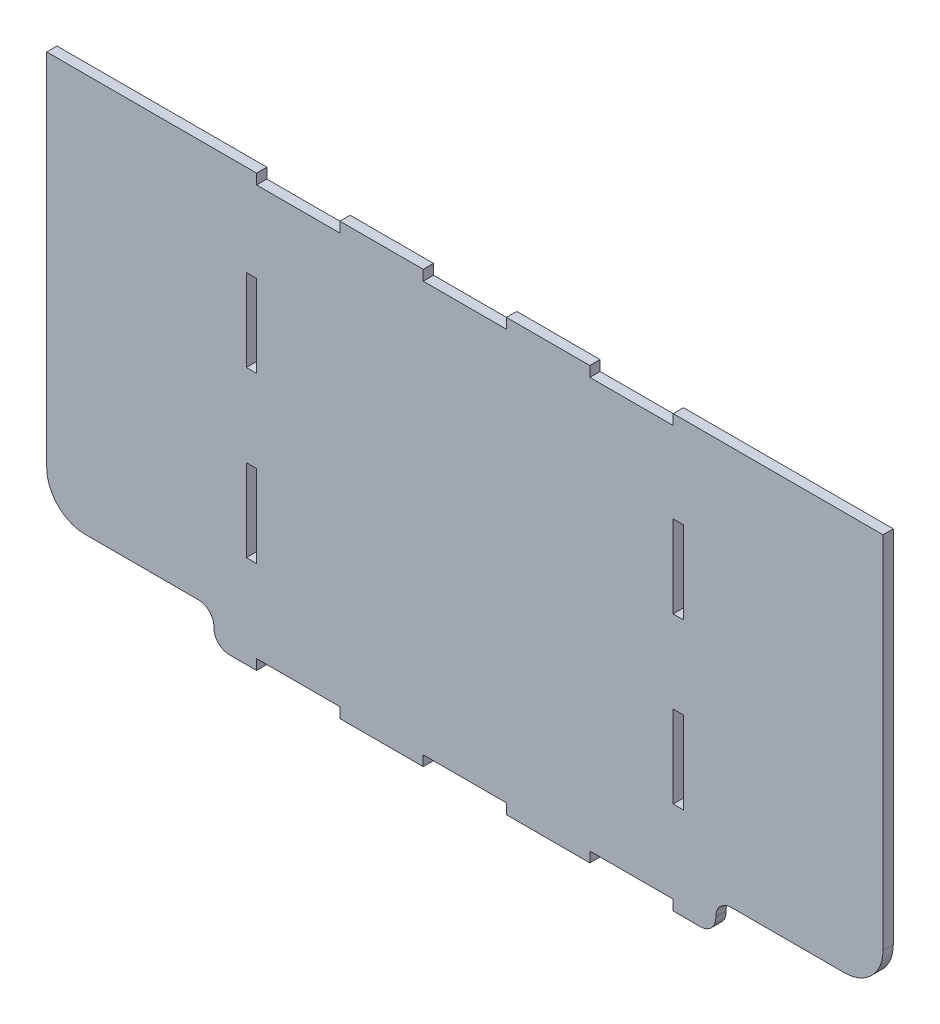
SolidWorks part; units mm, degrees
material "A-Glass Fiber"
ref_plane "Front Plane" through (0, 0, 0) normal (0, 0, 1) x (1, 0, 0)
ref_plane "Top Plane" through (0, 0, 0) normal (0, 1, 0) x (1, 0, 0)
ref_plane "Right Plane" through (0, 0, 0) normal (1, 0, 0) x (0, 0, -1)
sketch "Sketch1" plane through (0, 0, 0) normal (0, 0, 1) x (1, 0, 0)
  line L0 (0, 0) -> (1345.4471, 0)
  line L1 (212.2829, -469.9) -> (1133.1642, -469.9)
  line L2 (0, 0) -> (188.5098, -454.2888)
  line L3 (1345.4471, 0) -> (1156.9372, -454.2888)
  spline S1 degree 3 poles (1156.9372, -454.2888) (1155.9652, -456.6313) (1154.631, -458.8169) (1152.2259, -461.6935) (1151.3551, -462.5908) (1149.4733, -464.2609) (1148.4599, -465.0331) (1146.3603, -466.4012) (1145.2664, -467.0047) (1142.9909, -468.0521) (1141.799, -468.4985) (1138.1745, -469.5606) (1135.6993, -469.9116) (1133.1642, -469.9) knots 0 0 0 0 0.25 0.25 0.375 0.375 0.5 0.5 0.625 0.625 0.75 0.75 1 1 1 1
  spline S2 degree 3 poles (188.5098, -454.2888) (189.4819, -456.6313) (190.8161, -458.8169) (193.2211, -461.6935) (194.092, -462.5908) (195.9737, -464.2609) (196.9872, -465.0331) (199.0868, -466.4012) (200.1807, -467.0047) (202.4562, -468.0521) (203.6481, -468.4985) (207.2726, -469.5606) (209.7478, -469.9116) (212.2829, -469.9) knots 0 0 0 0 0.25 0.25 0.375 0.375 0.5 0.5 0.625 0.625 0.75 0.75 1 1 1 1
  dimension "D1" = 112.536
  dimension "D2" = 112.536
  dimension "D3" = 920.8813
  dimension "D4" = 469.9
extrude "Boss-Extrude1" add sketch "Sketch1" along normal blind 10.16
ref_plane "Plane1" through (672.7235, 0, 0) normal (1, 0, 0) x (0, 0, -1)
sketch "Sketch2" plane through (0, 0, 10.16) normal (0, 0, 1) x (1, 0, 0)
  line L0 (467.0082, -378.4231) -> (467.0082, -297.1061) construction
  line L1 (467.0082, -297.1061) -> (456.8417, -297.1061) construction
  line L2 (456.8417, -297.1061) -> (456.8417, -378.4231) construction
  line L3 (456.8417, -378.4231) -> (467.0082, -378.4231) construction
  line L4 (878.4388, -297.1061) -> (878.4388, -378.4231) construction
  line L5 (878.4388, -378.4231) -> (888.6053, -378.4231) construction
  line L6 (888.6053, -378.4231) -> (888.6053, -297.1061) construction
  line L7 (888.6053, -297.1061) -> (878.4388, -297.1061) construction
  line L8 (878.4388, -134.4722) -> (878.4388, -215.7892) construction
  line L9 (878.4388, -215.7892) -> (888.6053, -215.7892) construction
  line L10 (888.6053, -215.7892) -> (888.6053, -134.4722) construction
  line L11 (888.6053, -134.4722) -> (878.4388, -134.4722) construction
  line L24 (467.0082, -215.7892) -> (467.0082, -134.4722) construction
  line L25 (467.0082, -134.4722) -> (456.8417, -134.4722) construction
  line L26 (456.8417, -134.4722) -> (456.8417, -215.7892) construction
  line L27 (456.8417, -215.7892) -> (467.0082, -215.7892) construction
  line L28 (878.4388, -469.9) -> (878.4388, -459.74) construction
  line L29 (878.4388, -459.74) -> (796.1675, -459.74) construction
  line L30 (796.1675, -469.9) -> (796.1675, -459.74) construction
  line L31 (713.8592, -469.9) -> (713.8592, -459.74) construction
  line L32 (631.5879, -459.74) -> (713.8592, -459.74) construction
  line L33 (631.5879, -469.9) -> (631.5879, -459.74) construction
  line L34 (467.0082, -469.9) -> (467.0082, -459.74) construction
  line L35 (549.2795, -469.9) -> (549.2795, -459.74) construction
  line L36 (467.0082, -459.74) -> (549.2795, -459.74) construction
  line L37 (467.0082, -378.4231) -> (467.0082, -297.1061)
  line L38 (467.0082, -297.1061) -> (456.8417, -297.1061)
  line L39 (456.8417, -297.1061) -> (456.8417, -378.4231)
  line L40 (456.8417, -378.4231) -> (467.0082, -378.4231)
  line L41 (878.4388, -297.1061) -> (878.4388, -378.4231)
  line L42 (878.4388, -378.4231) -> (888.6053, -378.4231)
  line L43 (888.6053, -378.4231) -> (888.6053, -297.1061)
  line L44 (888.6053, -297.1061) -> (878.4388, -297.1061)
  line L45 (878.4388, -134.4722) -> (878.4388, -215.7892)
  line L46 (878.4388, -215.7892) -> (888.6053, -215.7892)
  line L47 (888.6053, -215.7892) -> (888.6053, -134.4722)
  line L48 (888.6053, -134.4722) -> (878.4388, -134.4722)
  line L61 (467.0082, -215.7892) -> (467.0082, -134.4722)
  line L62 (467.0082, -134.4722) -> (456.8417, -134.4722)
  line L63 (456.8417, -134.4722) -> (456.8417, -215.7892)
  line L64 (456.8417, -215.7892) -> (467.0082, -215.7892)
  line L65 (878.4388, -469.9) -> (878.4388, -459.74)
  line L66 (878.4388, -459.74) -> (796.1675, -459.74)
  line L67 (796.1675, -469.9) -> (796.1675, -459.74)
  line L68 (713.8592, -469.9) -> (713.8592, -459.74)
  line L69 (631.5879, -459.74) -> (713.8592, -459.74)
  line L70 (631.5879, -469.9) -> (631.5879, -459.74)
  line L71 (467.0082, -469.9) -> (467.0082, -459.74)
  line L72 (549.2795, -469.9) -> (549.2795, -459.74)
  line L73 (467.0082, -459.74) -> (549.2795, -459.74)
  line L74 (467.0082, -469.9) -> (549.2795, -469.9)
  line L75 (631.5879, -469.9) -> (713.8592, -469.9)
  line L76 (796.1675, -469.9) -> (878.4388, -469.9)
extrude "Cut-Extrude2" cut sketch "Sketch2" against normal blind 137.414
sketch "Sketch4" plane through (0, 0, 10.16) normal (0, 0, 1) x (1, 0, 0)
  line L0 (0, 0) -> (1345.4471, 0)
  line L1 (1345.4471, 0) -> (1327.0023, -44.45)
  line L2 (1156.9372, -454.2888) -> (1345.4471, 0) construction
  line L3 (1327.0023, -44.45) -> (18.4448, -44.45)
  line L4 (0, 0) -> (188.5098, -454.2888) construction
  line L5 (18.4448, -44.45) -> (0, 0)
  dimension "D1" = 44.45
extrude "Cut-Extrude3" cut sketch "Sketch4" against normal through all
sketch "Sketch5" plane through (0, 0, 10.16) normal (0, 0, 1) x (1, 0, 0)
  line L0 (672.7235, -5.588) -> (672.7235, 5.588) construction
  line L1 (713.8715, -54.61) -> (631.5755, -54.61)
  line L2 (713.8715, -54.61) -> (713.8715, -44.45)
  line L3 (713.8715, -44.45) -> (631.5755, -44.45)
  line L4 (631.5755, -54.61) -> (631.5755, -44.45)
  line L5 (713.8715, -54.61) -> (631.5755, -44.45) construction
  line L6 (713.8715, -44.45) -> (631.5755, -54.61) construction
  line L7 (18.4448, -44.45) -> (1327.0023, -44.45) construction
  line L9 (631.5755, -44.45) -> (549.2795, -44.45)
  line L10 (631.5755, -44.45) -> (631.5755, -54.61)
  line L11 (631.5755, -54.61) -> (549.2795, -54.61)
  line L12 (549.2795, -44.45) -> (549.2795, -54.61)
  line L13 (549.2795, -44.45) -> (466.9835, -44.45)
  line L14 (549.2795, -44.45) -> (549.2795, -54.61)
  line L15 (549.2795, -54.61) -> (466.9835, -54.61)
  line L16 (466.9835, -44.45) -> (466.9835, -54.61)
  line L17 (713.8715, -44.45) -> (796.1675, -44.45)
  line L18 (713.8715, -44.45) -> (713.8715, -54.61)
  line L19 (713.8715, -54.61) -> (796.1675, -54.61)
  line L20 (796.1675, -44.45) -> (796.1675, -54.61)
  line L21 (796.1675, -44.45) -> (878.4635, -44.45)
  line L22 (796.1675, -44.45) -> (796.1675, -54.61)
  line L23 (796.1675, -54.61) -> (878.4635, -54.61)
  line L24 (878.4635, -44.45) -> (878.4635, -54.61)
  point P0 (672.7235, -49.53)
  line M26 (1327.0023, -44.45) -> (18.4448, -44.45)
  dimension "D1" = 82.296
  dimension "D2" = 10.16
extrude "Cut-Extrude4" cut sketch "Sketch5" against normal through all contours L16 L15 L12 M26 | L4 L1 L2 M26 | L24 L20 L23 M26 region at (672.7235, -49.53, 10.16) region at (837.3155, -49.53, 10.16) region at (508.1315, -49.53, 10.16)
sketch "Sketch6" plane through (0, 0, 10.16) normal (0, 0, 1) x (1, 0, 0)
  line L0 (192.8075, -448.0779) -> (224.9829, -469.9)
  line L2 (212.2829, -469.9) -> (467.0082, -469.9) construction
  line L4 (56.5448, -44.45) -> (56.5448, -119.699)
  line L5 (24.3099, -42.0162) -> (194.3749, -451.8551)
  line L6 (56.5448, -119.699) -> (192.8075, -448.0779)
  line L7 (18.4448, -44.45) -> (466.9835, -44.45) construction
  line L9 (56.5448, -44.45) -> (-120.2389, 37.3825)
  line L10 (-120.2389, 37.3825) -> (-59.5107, -242.3351)
  line L11 (-59.5107, -242.3351) -> (232.0802, -549.7664)
  line L12 (224.9829, -469.9) -> (232.0802, -549.7664)
  line L13 (672.7235, -54.61) -> (672.7235, -459.74) construction
  line L14 (713.8715, -54.61) -> (631.5755, -54.61) construction
  line L15 (713.8592, -459.74) -> (631.5879, -459.74) construction
  line L16 (1120.4642, -469.9) -> (1113.3668, -549.7664)
  line L17 (1404.9578, -242.3351) -> (1113.3668, -549.7664)
  line L18 (1465.686, 37.3825) -> (1404.9578, -242.3351)
  line L19 (1288.9023, -44.45) -> (1465.686, 37.3825)
  line L20 (1288.9023, -119.699) -> (1152.6395, -448.0779)
  line L21 (1288.9023, -44.45) -> (1288.9023, -119.699)
  line L22 (1152.6395, -448.0779) -> (1120.4642, -469.9)
  dimension "D1" = 12.7
  dimension "D2" = 38.1
  dimension "D3" = 6.35
extrude "Cut-Extrude5" cut sketch "Sketch6" against normal through all
sketch "Sketch7" plane through (0, 0, 10.16) normal (0, 0, 1) x (1, 0, 0)
  line L1 (335.9448, -469.9) -> (-145.5373, -469.9)
  line L2 (259.7448, -393.7) -> (259.7448, 127.8863)
  line L3 (259.7448, 127.8863) -> (-145.5373, 127.8863)
  line L4 (-145.5373, -469.9) -> (-145.5373, 127.8863)
  line L5 (1009.5023, -469.9) -> (1351.8588, -469.9)
  line L6 (1085.7023, -393.7) -> (1085.7023, 23.6984)
  line L7 (1085.7023, 23.6984) -> (1351.8588, 23.6984)
  line L8 (1351.8588, -469.9) -> (1351.8588, 23.6984)
  line L9 (672.7235, -459.74) -> (672.7235, 43.7275) construction
  line L10 (713.8592, -459.74) -> (631.5879, -459.74) construction
  line L11 (672.7235, -5.588) -> (672.7235, 5.588) construction
  line L12 (1047.6023, -438.15) -> (935.8423, -438.15)
  line L13 (920.6023, -453.39) -> (920.6023, -454.66)
  line L14 (297.8448, -438.15) -> (409.6048, -438.15)
  line L15 (424.8448, -453.39) -> (424.8448, -454.66)
  line L25 (259.7448, -393.7) -> (259.7448, -400.05)
  line L26 (1085.7023, -393.7) -> (1085.7023, -400.05)
  line L44 (56.5448, -44.45) -> (56.5448, -119.699)
  line L45 (466.9835, -44.45) -> (56.5448, -44.45)
  line L46 (466.9835, -54.61) -> (466.9835, -44.45)
  line L47 (549.2795, -54.61) -> (466.9835, -54.61)
  line L48 (549.2795, -44.45) -> (549.2795, -54.61)
  line L49 (631.5755, -44.45) -> (549.2795, -44.45)
  line L50 (631.5755, -54.61) -> (631.5755, -44.45)
  line L51 (713.8715, -54.61) -> (631.5755, -54.61)
  line L52 (713.8715, -44.45) -> (713.8715, -54.61)
  line L53 (796.1675, -44.45) -> (713.8715, -44.45)
  line L54 (796.1675, -54.61) -> (796.1675, -44.45)
  line L55 (878.4635, -54.61) -> (796.1675, -54.61)
  line L56 (878.4635, -44.45) -> (878.4635, -54.61)
  line L57 (1288.9023, -44.45) -> (878.4635, -44.45)
  line L58 (1288.9023, -119.699) -> (1288.9023, -44.45)
  line L59 (1152.6395, -448.0779) -> (1288.9023, -119.699)
  line L60 (1120.4642, -469.9) -> (1152.6395, -448.0779)
  line L61 (878.4388, -469.9) -> (1120.4642, -469.9)
  line L62 (878.4388, -459.74) -> (878.4388, -469.9)
  line L63 (796.1675, -459.74) -> (878.4388, -459.74)
  line L64 (796.1675, -469.9) -> (796.1675, -459.74)
  line L65 (713.8592, -469.9) -> (796.1675, -469.9)
  line L66 (713.8592, -459.74) -> (713.8592, -469.9)
  line L67 (631.5879, -459.74) -> (713.8592, -459.74)
  line L68 (631.5879, -469.9) -> (631.5879, -459.74)
  line L69 (549.2795, -469.9) -> (631.5879, -469.9)
  line L70 (549.2795, -459.74) -> (549.2795, -469.9)
  line L71 (467.0082, -459.74) -> (549.2795, -459.74)
  line L72 (467.0082, -469.9) -> (467.0082, -459.74)
  line L73 (224.9829, -469.9) -> (467.0082, -469.9)
  line L74 (192.8075, -448.0779) -> (224.9829, -469.9)
  line L75 (56.5448, -119.699) -> (192.8075, -448.0779)
  line L76 (56.5448, -44.45) -> (56.5448, -119.699)
  line L77 (466.9835, -44.45) -> (56.5448, -44.45)
  line L78 (466.9835, -54.61) -> (466.9835, -44.45)
  line L79 (549.2795, -54.61) -> (466.9835, -54.61)
  line L80 (549.2795, -44.45) -> (549.2795, -54.61)
  line L81 (631.5755, -44.45) -> (549.2795, -44.45)
  line L82 (631.5755, -54.61) -> (631.5755, -44.45)
  line L83 (713.8715, -54.61) -> (631.5755, -54.61)
  line L84 (713.8715, -44.45) -> (713.8715, -54.61)
  line L85 (796.1675, -44.45) -> (713.8715, -44.45)
  line L86 (796.1675, -54.61) -> (796.1675, -44.45)
  line L87 (878.4635, -54.61) -> (796.1675, -54.61)
  line L88 (878.4635, -44.45) -> (878.4635, -54.61)
  line L89 (1288.9023, -44.45) -> (878.4635, -44.45)
  line L90 (1288.9023, -119.699) -> (1288.9023, -44.45)
  line L91 (1152.6395, -448.0779) -> (1288.9023, -119.699)
  line L92 (1120.4642, -469.9) -> (1152.6395, -448.0779)
  line L93 (878.4388, -469.9) -> (905.3623, -469.9)
  line L94 (878.4388, -459.74) -> (878.4388, -469.9)
  line L95 (796.1675, -459.74) -> (878.4388, -459.74)
  line L96 (796.1675, -469.9) -> (796.1675, -459.74)
  line L97 (713.8592, -469.9) -> (796.1675, -469.9)
  line L98 (713.8592, -459.74) -> (713.8592, -469.9)
  line L99 (631.5879, -459.74) -> (713.8592, -459.74)
  line L100 (631.5879, -469.9) -> (631.5879, -459.74)
  line L101 (549.2795, -469.9) -> (631.5879, -469.9)
  line L102 (549.2795, -459.74) -> (549.2795, -469.9)
  line L103 (467.0082, -459.74) -> (549.2795, -459.74)
  line L104 (467.0082, -469.9) -> (467.0082, -459.74)
  line L105 (440.0848, -469.9) -> (467.0082, -469.9)
  line L106 (192.8075, -448.0779) -> (224.9829, -469.9)
  line L107 (56.5448, -119.699) -> (192.8075, -448.0779)
  arc A2 (297.8448, -438.15) -> (259.7448, -400.05) centre (297.8448, -400.05) cw
  arc A3 (1047.6023, -438.15) -> (1085.7023, -400.05) centre (1047.6023, -400.05) ccw
  arc A4 (440.0848, -469.9) -> (424.8448, -454.66) centre (440.0848, -454.66) cw
  arc A5 (409.6048, -438.15) -> (424.8448, -453.39) centre (409.6048, -453.39) cw
  arc A6 (920.6023, -454.66) -> (905.3623, -469.9) centre (905.3623, -454.66) cw
  arc A7 (935.8423, -438.15) -> (920.6023, -453.39) centre (935.8423, -453.39) ccw
  point P32 (424.8448, -438.15)
  point P52 (920.6023, -438.15)
  line M21 (466.9835, -44.45) -> (56.5448, -44.45)
  line M22 (56.5448, -44.45) -> (56.5448, -119.699)
  line M23 (56.5448, -119.699) -> (192.8075, -448.0779)
  line M24 (192.8075, -448.0779) -> (224.9829, -469.9)
  line M25 (224.9829, -469.9) -> (467.0082, -469.9)
  line M37 (878.4388, -469.9) -> (1120.4642, -469.9)
  line M38 (1120.4642, -469.9) -> (1152.6395, -448.0779)
  line M39 (1152.6395, -448.0779) -> (1288.9023, -119.699)
  line M40 (1288.9023, -119.699) -> (1288.9023, -44.45)
  line M41 (1288.9023, -44.45) -> (878.4635, -44.45)
  dimension "D1" = 38.1
  dimension "D9" = 15.24
  dimension "D8" = 15.24
  dimension "D2" = 203.2
  dimension "D3" = 1497.3961
  dimension "D4" = 0
  dimension "D5" = 62.9565
  dimension "D6" = 127
  dimension "D7" = 127
extrude "Cut-Extrude6" cut sketch "Sketch7" against normal blind 25.4 contours L6 M37 M38 M39 M40 M41 | L2 M21 M22 M23 M24 M25 region at (193.4413, -235.948, 10.16) region at (1152.0058, -235.948, 10.16)
